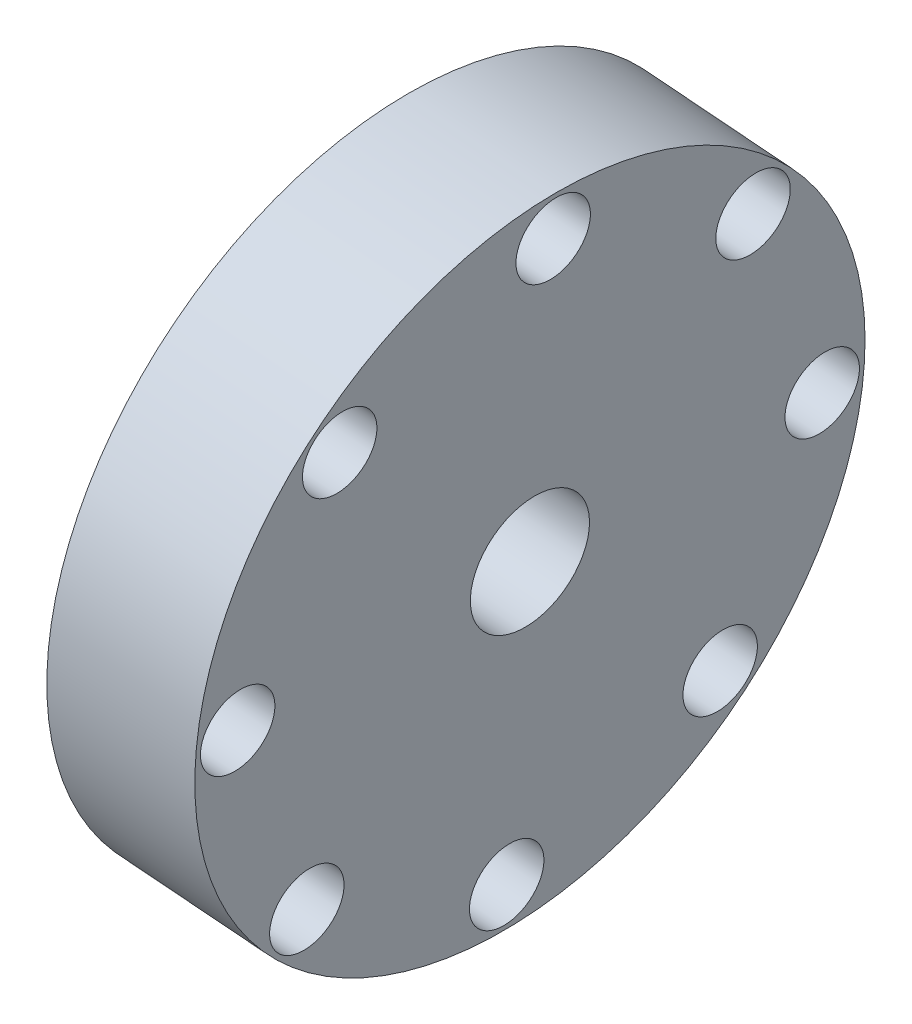
SolidWorks part; units mm, degrees
ref_plane "Front Plane" through (0, 0, 0) normal (0, 0, 1) x (1, 0, 0)
ref_plane "Top Plane" through (0, 0, 0) normal (0, 1, 0) x (1, 0, 0)
ref_plane "Right Plane" through (0, 0, 0) normal (1, 0, 0) x (0, 0, -1)
sketch "Sketch1" plane through (234.2789, -18.689, 0) normal (0.9968, -0.0795, 0) x (0, 0, -1)
  circle A1 centre (-43.1743, 8.5503) radius 14.2875
  dimension "D1" = 28.575
extrude "Boss-Extrude1" add sketch "Sketch1" against normal blind 6.35
sketch "Sketch2" plane through (234.2789, -18.689, 0) normal (0.9968, -0.0795, 0) x (0, 0, -1)
  circle A0 centre (-43.1743, 8.5503) radius 2.54
extrude "Cut-Extrude1" cut sketch "Sketch2" against normal blind 5.08
sketch "Sketch3" plane through (227.949, -18.1841, 0) normal (-0.9968, 0.0795, 0) x (0, 0, 1)
  circle A0 centre (43.1743, 21.0503) radius 1.5875
  circle A1 centre (43.1743, 8.5503) radius 14.2875 construction
  circle A2 centre (43.1743, 8.5503) radius 14.2875
  circle A3 centre (52.0131, 17.3892) radius 1.5875
  circle A4 centre (55.6743, 8.5503) radius 1.5875
  circle A5 centre (52.0131, -0.2885) radius 1.5875
  circle A6 centre (43.1743, -3.9497) radius 1.5875
  circle A7 centre (34.3354, -0.2885) radius 1.5875
  circle A8 centre (30.6743, 8.5503) radius 1.5875
  circle A9 centre (34.3354, 17.3892) radius 1.5875
  point P21 (43.1743, 8.5503)
  dimension "D1" = 3.175
  dimension "D3" = 12.5
  dimension "D2" = 8
extrude "Cut-Extrude2" cut sketch "Sketch3" against normal blind 10 contours A8 | A0 | A3 | A4 | A5 | A6 | A7 | A9 region at (229.6229, 2.7996, 43.1743) region at (229.3318, -0.85, 52.0131) region at (228.6289, -9.6608, 55.6743) region at (227.926, -18.4717, 52.0131) region at (227.6349, -22.1212, 43.1743) region at (227.926, -18.4717, 34.3354) region at (228.6289, -9.6608, 30.6743)
